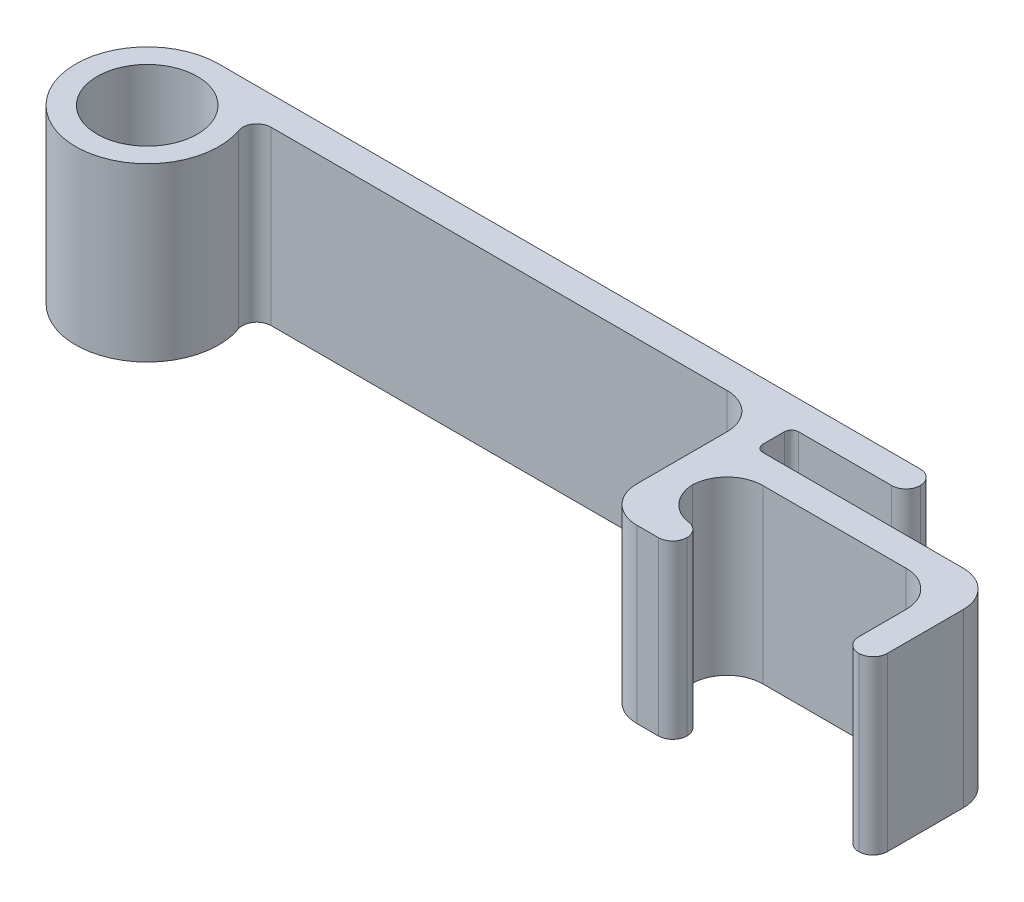
SolidWorks part; units mm, degrees
ref_plane "Front Plane" through (0, 0, 0) normal (0, 0, 1) x (1, 0, 0)
ref_plane "Top Plane" through (0, 0, 0) normal (0, 1, 0) x (1, 0, 0)
ref_plane "Right Plane" through (0, 0, 0) normal (1, 0, 0) x (0, 0, -1)
sketch "Sketch1" plane through (0, 0, 0) normal (0, 1, 0) x (1, 0, 0)
  circle A0 centre (0, 0) radius 5
  dimension "D1" = 10
extrude "Boss-Extrude1" add sketch "Sketch1" along normal blind 12
sketch "Sketch2" plane through (0, 12, 0) normal (0, 1, 0) x (1, 0, 0)
  circle A0 centre (0, 0) radius 3.5
  dimension "D1" = 7
extrude "Cut-Extrude1" cut sketch "Sketch2" against normal through all
sketch "Sketch3" plane through (0, 12, 0) normal (0, 1, 0) x (1, 0, 0)
  line L0 (0, 5) -> (50, 5)
  line L1 (50, 3) -> (4, 3)
  line L2 (50, 3) -> (50, 5)
  circle A0 centre (0, 0) radius 5 construction
  arc A2 (0, 5) -> (4, 3) centre (0, 0) cw
  dimension "D1" = 2
  dimension "D2" = 50
extrude "Boss-Extrude2" add sketch "Sketch3" against normal blind 12
sketch "Sketch4" plane through (0, 12, 0) normal (0, 1, 0) x (1, 0, 0)
  line L0 (40, 3) -> (40, -8.3)
  line L1 (4, 3) -> (50, 3) construction
  line L2 (50, 3) -> (50, 5) construction
  line L3 (50, 5) -> (0, 5) construction
  line L4 (40, -8.3) -> (45, -8.3)
  line L5 (45, -8.3) -> (45, -6.3)
  line L6 (45, -6.3) -> (42, -6.3)
  line L7 (42, -6.3) -> (42, 3)
  line L8 (42, 3) -> (40, 3)
  dimension "D1" = 10
  dimension "D2" = 13.3
  dimension "D3" = 5
  dimension "D4" = 2
  dimension "D5" = 2
extrude "Boss-Extrude3" add sketch "Sketch4" against normal blind 12
sketch "Sketch6" plane through (0, 12, 0) normal (0, 1, 0) x (1, 0, 0)
  line L0 (42, -6.3) -> (42, 3) construction
  line L1 (42, 0.5) -> (59, 0.5)
  line L2 (42, 0.5) -> (42, -1.5)
  line L3 (42, -1.5) -> (57, -1.5)
  line L4 (59, 0.5) -> (59, -1.5)
  line L5 (42, 3) -> (50, 3) construction
  line L7 (59, -1.5) -> (59, -8.3)
  line L8 (59, -8.3) -> (57, -8.3)
  line L9 (57, -8.3) -> (57, -1.5)
  dimension "D1" = 2
  dimension "D2" = 2.5
  dimension "D3" = 17
  dimension "D4" = 2
extrude "Boss-Extrude4" add sketch "Sketch6" against normal blind 12
fillet "Fillet1" radius 1 6 edges at (59, 6, 8.3) (57, 6, 8.3) (45, 6, 8.3) (45, 6, 6.3) (50, 6, -5) (50, 6, -3)
fillet "Fillet2" radius 2.5 5 edges at (57, 6, 1.5) (59, 6, -0.5) (40, 6, 8.3) (42, 6, 6.3) (42, 6, 1.5)
fillet "Fillet3" radius 2.5 1 edges at (40, 6, -3)
fillet "Fillet4" radius 1 1 edges at (4, 6, -3)
fillet "Fillet5" radius 0.5 2 edges at (42, 6, -0.5) (42, 6, -3)
sketch "Sketch7" plane through (0, 0, -5) normal (0, 0, -1) x (-1, 0, 0)
  text T0 "<b>Alex Fare</b>"
extrude "Cut-Extrude2" cut sketch "Sketch7" against normal blind 0.5
